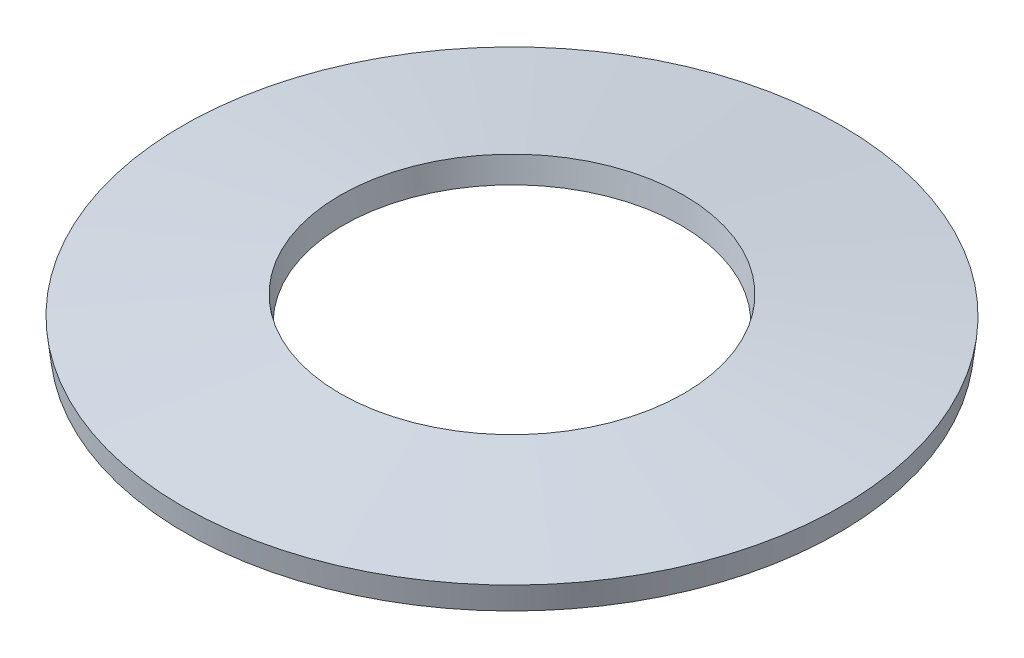
SolidWorks part; units mm, degrees
ref_plane "Front Plane" through (0, 0, 0) normal (0, 0, 1) x (1, 0, 0)
ref_plane "Top Plane" through (0, 0, 0) normal (0, 1, 0) x (1, 0, 0)
ref_plane "Right Plane" through (0, 0, 0) normal (1, 0, 0) x (0, 0, -1)
sketch "Sketch1" plane through (0, 0, 0) normal (0, 0, 1) x (1, 0, 0)
  line L0 (7.9293, 0) -> (4.1, 0.4542)
  line L1 (4.1, 0.4542) -> (4.1707, 1.05)
  line L2 (4.1707, 1.05) -> (8, 0.5958)
  line L3 (8, 0.5958) -> (7.9293, 0)
  line L4 (0, 0) -> (0, 1.05) construction
  line L5 (-8, 0.5958) -> (-7.9293, 0) construction
  line L6 (-4.1707, 1.05) -> (-8, 0.5958) construction
  line L7 (-4.1, 0.4542) -> (-4.1707, 1.05) construction
  line L8 (-7.9293, 0) -> (-4.1, 0.4542) construction
  point P5 (4.1353, 0.7521)
  point P8 (-4.1353, 0.7521)
  dimension "D1" = 3.8562
  dimension "ID" = 8.2
  dimension "OD" = 16
  dimension "Thickness" = 0.6
  dimension "Height" = 1.05
revolve "Revolve1" add sketch "Sketch1" angle 360 about L4
sketch "Sketch15" plane through (0, 0, 0) normal (0, 1, 0) x (1, 0, 0)
  circle A0 centre (0, 0) radius 8
  circle A1 centre (0, 0) radius 4.1
ref_axis "Axis1" through (0, 1.05, 0) along (0, -1, 0)
